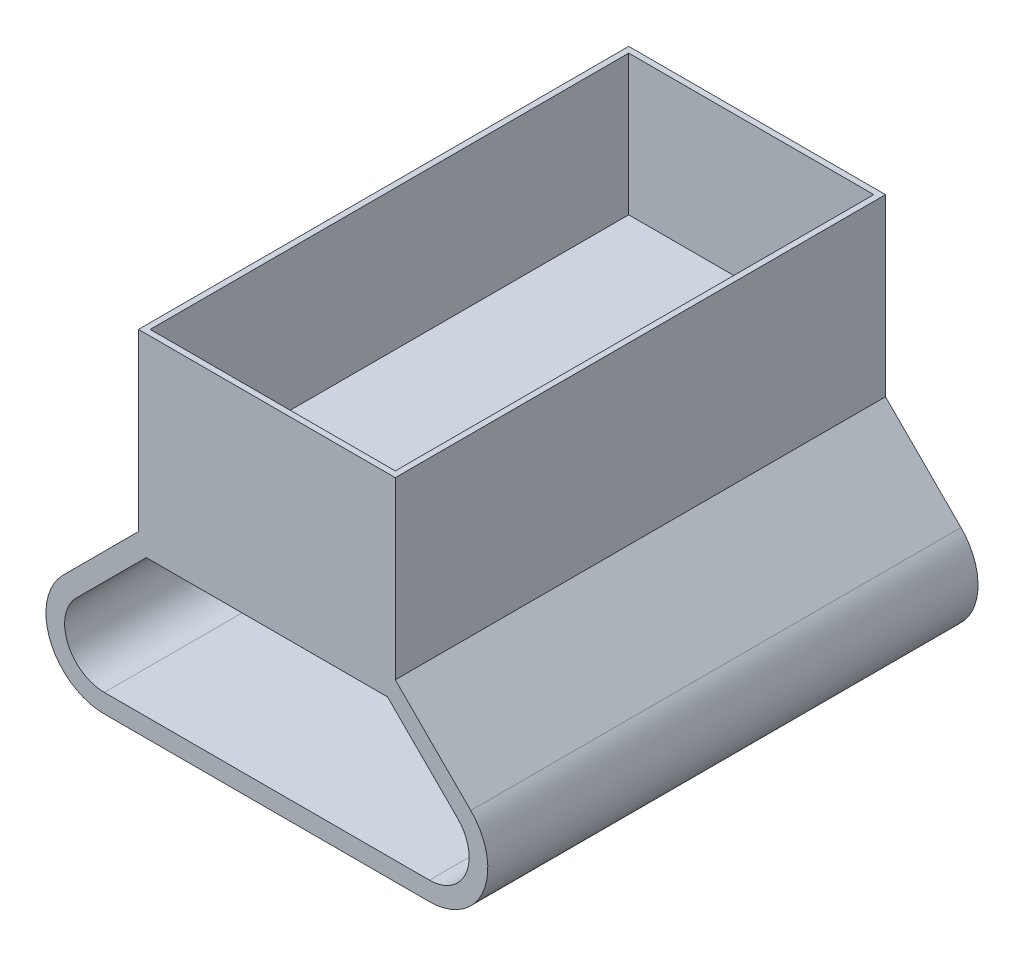
SolidWorks part; units mm, degrees
ref_plane "Front Plane" through (0, 0, 0) normal (0, 0, 1) x (1, 0, 0)
ref_plane "Top Plane" through (0, 0, 0) normal (0, 1, 0) x (1, 0, 0)
ref_plane "Right Plane" through (0, 0, 0) normal (1, 0, 0) x (0, 0, -1)
sketch "Sketch1" plane through (0, 0, 0) normal (0, 0, 1) x (1, 0, 0)
  line L0 (-11, 0) -> (11, 0)
  line L1 (-11, 0) -> (-17.4645, -6.4645)
  line L2 (-13.9289, -15) -> (13.9289, -15)
  line L3 (17.4645, -6.4645) -> (11, 0)
  arc A0 (-17.4645, -6.4645) -> (-13.9289, -15) centre (-13.9289, -10) ccw
  arc A1 (13.9289, -15) -> (17.4645, -6.4645) centre (13.9289, -10) ccw
  point P3 (-2.6993, 0)
  point P4 (0, 0)
  point P6 (0, 0)
  point P8 (-26.4535, -21.1639)
  point P9 (-33.5712, -21.6785)
  point P10 (-15.8198, 0)
  point P11 (-29.6264, -23.1363)
  point P12 (-16.9347, 0)
  point P13 (-16.3344, 0)
  point P14 (-16.4633, 0)
  point P15 (-33.2222, -17.6443)
  point P16 (-24.3682, -13.3682)
  point P17 (-26.5483, -15.5483)
  point P18 (-27.568, -16.568)
  dimension "D4" = 5
  dimension "D1" = 45
  dimension "D2" = 22
  dimension "D3" = 15
extrude "Boss-Extrude1" add sketch "Sketch1" along normal blind 42
sketch "Sketch3" plane through (0, 0, 42) normal (0, 0, 1) x (1, 0, 0)
  line L27 (-13.9289, -13.4) -> (13.9289, -13.4)
  line L28 (16.3331, -7.5958) -> (10.3373, -1.6)
  line L29 (10.3373, -1.6) -> (-10.3373, -1.6)
  line L30 (-10.3373, -1.6) -> (-16.3331, -7.5958)
  line L31 (-13.9289, -13.4) -> (13.9289, -13.4)
  line L32 (16.3331, -7.5958) -> (10.3373, -1.6)
  line L33 (10.3373, -1.6) -> (-10.3373, -1.6)
  line L34 (-10.3373, -1.6) -> (-16.3331, -7.5958)
  arc A6 (13.9289, -13.4) -> (16.3331, -7.5958) centre (13.9289, -10) ccw
  arc A7 (-16.3331, -7.5958) -> (-13.9289, -13.4) centre (-13.9289, -10) ccw
  arc A8 (13.9289, -13.4) -> (16.3331, -7.5958) centre (13.9289, -10) ccw
  arc A9 (-16.3331, -7.5958) -> (-13.9289, -13.4) centre (-13.9289, -10) ccw
  dimension "D1" = 1.6
extrude "Cut-Extrude1" cut sketch "Sketch3" against normal through all
sketch "Sketch2" plane through (0, 0, 0) normal (0, 1, 0) x (1, 0, 0)
  line L1 (-11, 0) -> (11, 0)
  line L2 (-11, 0) -> (-11, -42)
  line L3 (-11, -42) -> (11, -42)
  line L4 (11, 0) -> (11, -42)
  line L5 (-10.5, -0.5) -> (10.5, -0.5)
  line L6 (-10.5, -0.5) -> (-10.5, -41.5)
  line L7 (-10.5, -41.5) -> (10.5, -41.5)
  line L8 (10.5, -0.5) -> (10.5, -41.5)
  point P10 (-10.1511, -0.5328)
  point P11 (-10.4245, -0.4872)
  point P13 (0, -0.5)
  point P14 (-10.5, -21)
  point P15 (-11, -21)
  dimension "D1" = 41
  dimension "D2" = 21
extrude "Boss-Extrude2" add sketch "Sketch2" along normal blind 15
extrude "Boss-Extrude3" add sketch "Sketch2<2>" along normal blind 3 contours L8 L5 L6 L7 region at (0, 0, 21)
sketch "Sketch2<2>" plane through (0, 0, 0) normal (0, 1, 0) x (1, 0, 0) same geometry as "Sketch2"
